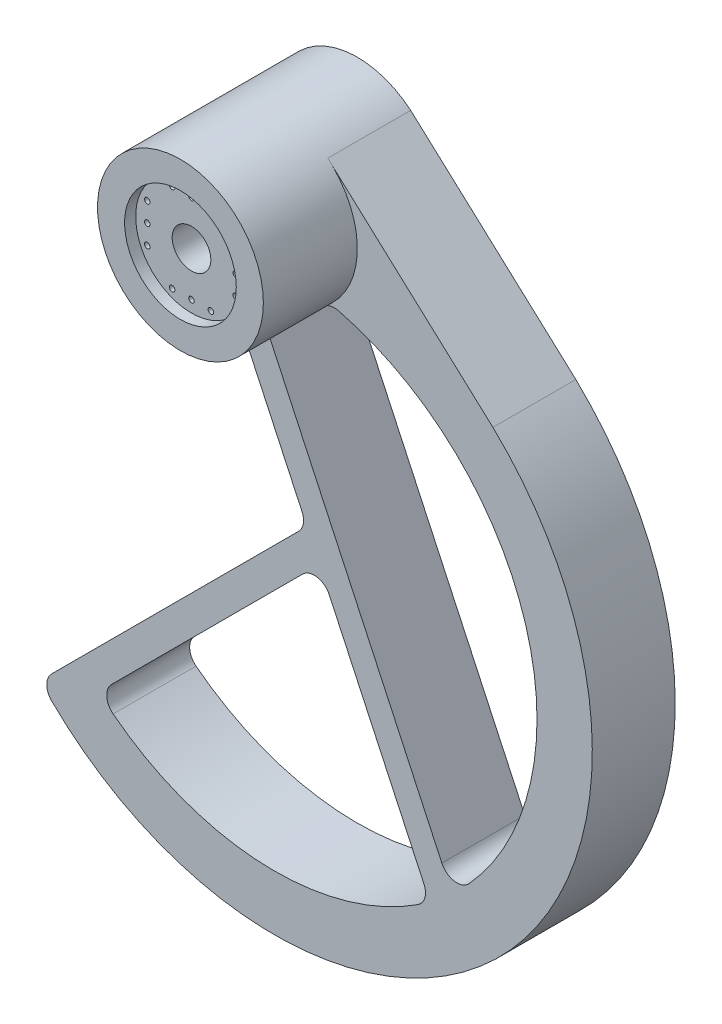
SolidWorks part; units mm, degrees
material "ABS"
ref_plane "正面" through (0, 0, 0) normal (0, 0, 1) x (1, 0, 0)
ref_plane "平面" through (0, 0, 0) normal (0, 1, 0) x (1, 0, 0)
ref_plane "右側面" through (0, 0, 0) normal (1, 0, 0) x (0, 0, -1)
sketch "ｽｹｯﾁ1" plane through (0, 0, 0) normal (0, 0, 1) x (1, 0, 0)
  line L1 (9.9336, 0.7043) -> (27.0462, -35.9938)
  line L2 (9.6418, 68.9907) -> (39.5241, 41.7624)
  line L4 (4.3888, 7.9244) -> (-40.3035, -36.7679)
  line L5 (5.0933, 1.5578) -> (-29.4572, -32.9928)
  line L6 (-13.5946, 51.1607) -> (4.9864, 11.3135)
  line L7 (30.2877, -31.1143) -> (-2.0547, 38.2444)
  arc A0 (-40.2839, -41.0299) -> (37.9168, 43.2269) centre (0, 0) ccw
  arc A1 (-29.1788, -37.4813) -> (25.9673, -39.7737) centre (0, 0) ccw
  arc A2 (0.5535, 42.5102) -> (9.0577, 45.5435) centre (0, 57.5) ccw
  arc A3 (35.2318, -31.8586) -> (11.602, 46.0613) centre (0, 0) ccw
  arc A4 (10.5469, 68.1659) -> (-13.5946, 51.1607) centre (0, 57.5) ccw
  arc A5 (-40.3035, -36.7679) -> (-40.2839, -41.0299) centre (-38.1821, -38.8893) ccw
  arc A6 (-29.4572, -32.9928) -> (-29.1788, -37.4813) centre (-27.3359, -35.1141) ccw
  arc A7 (27.0462, -35.9938) -> (25.9673, -39.7737) centre (24.3273, -37.2617) cw
  arc A8 (5.0933, 1.5578) -> (9.9336, 0.7043) centre (7.2147, -0.5635) cw
  arc A9 (35.2318, -31.8586) -> (30.2877, -31.1143) centre (33.0067, -29.8464) cw
  arc A10 (4.9864, 11.3135) -> (4.3888, 7.9244) centre (2.2675, 10.0457) cw
  arc A11 (-2.0547, 38.2444) -> (0.5535, 42.5102) centre (0.6642, 39.5123) cw
  arc A12 (11.602, 46.0613) -> (9.0577, 45.5435) centre (10.8692, 43.1522) ccw
  point P24 (8.1229, 4.5874)
  dimension "D1" = 3
  dimension "D2" = 3
  dimension "D3" = 3
  dimension "D4" = 3
  dimension "D5" = 3
  dimension "D6" = 3
  dimension "D7" = 3
  dimension "D8" = 3
extrude "ﾎﾞｽ - 押し出し1" add sketch "ｽｹｯﾁ1" along normal blind 15 contours L6 A10 L4 A5 A0 L2 A4 A12 A3 A9 L7 A11 A2 L5 A8 L1 A7 A1 A6 region at (8.9951, 67.3719, 0)
sketch "ｽｹｯﾁ6" plane through (0, 0, 15) normal (0, 0, 1) x (1, 0, 0)
  circle A0 centre (0, 57.5) radius 3.5
extrude "ｶｯﾄ - 押し出し2" cut sketch "ｽｹｯﾁ6" against normal blind 15
sketch "ｽｹｯﾁ9" plane through (0, 0, 15) normal (0, 0, 1) x (1, 0, 0)
  circle A0 centre (0, 57.5) radius 15
  circle A1 centre (0, 57.5) radius 3.5
extrude "ﾎﾞｽ - 押し出し2" add sketch "ｽｹｯﾁ9" along normal blind 17
sketch "ｽｹｯﾁ10" plane through (0, 0, 32) normal (0, 0, 1) x (1, 0, 0)
  circle A0 centre (0, 57.5) radius 10.1
extrude "ｶｯﾄ - 押し出し5" cut sketch "ｽｹｯﾁ10" against normal blind 2
sketch "ｽｹｯﾁ11" plane through (0, 0, 30) normal (0, 0, 1) x (1, 0, 0)
  line L0 (0, 65.5) -> (-3.5, 65.5) construction
  line L1 (0, 57.5) -> (0, 65.5) construction
  line L2 (0, 65.5) -> (3.5, 65.5) construction
  circle A0 centre (-3.5, 65.5) radius 0.5
  circle A1 centre (0, 65.5) radius 0.5
  circle A2 centre (3.5, 65.5) radius 0.5
  circle A3 centre (8, 57.5) radius 0.5
  circle A4 centre (8, 61) radius 0.5
  circle A5 centre (8, 54) radius 0.5
  circle A6 centre (0, 49.5) radius 0.5
  circle A7 centre (3.5, 49.5) radius 0.5
  circle A8 centre (-3.5, 49.5) radius 0.5
  circle A9 centre (-8, 57.5) radius 0.5
  circle A10 centre (-8, 54) radius 0.5
  circle A11 centre (-8, 61) radius 0.5
  point P25 (0, 57.5)
extrude "ｶｯﾄ - 押し出し6" cut sketch "ｽｹｯﾁ11" against normal blind 3
